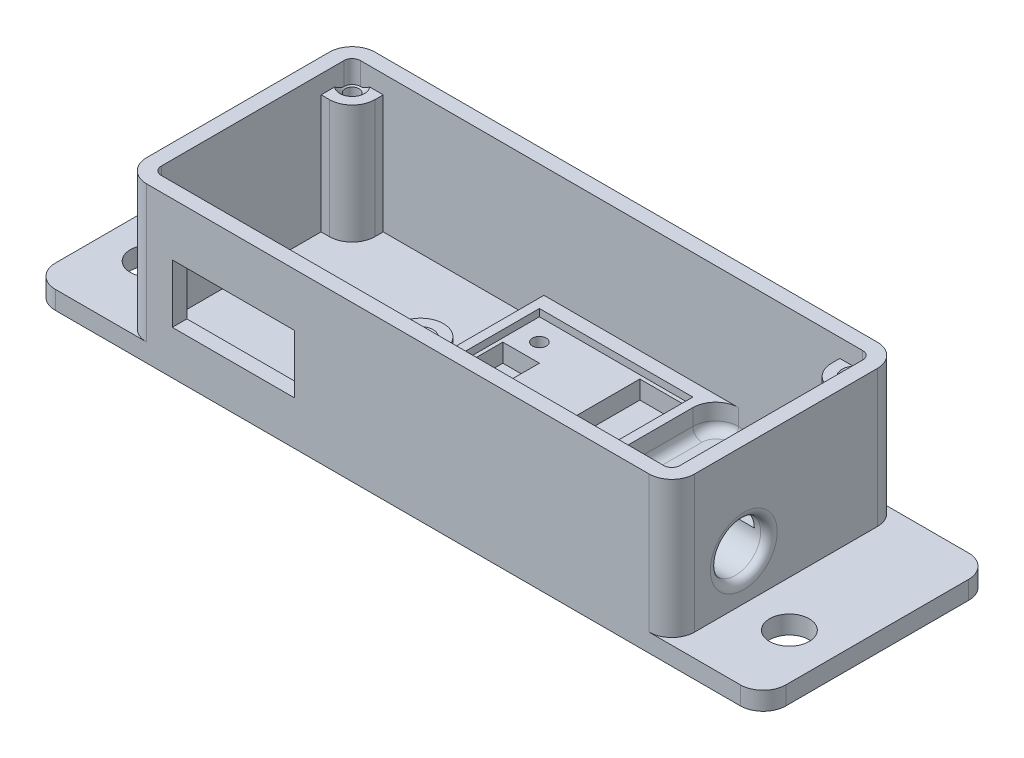
SolidWorks part; units mm, degrees
ref_plane "Plane XZ" through (0, 0, 0) normal (0, 0, 1) x (1, 0, 0)
ref_plane "Plane XY" through (0, 0, 0) normal (0, 1, 0) x (1, 0, 0)
ref_plane "Plane YZ" through (0, 0, 0) normal (1, 0, 0) x (0, 0, -1)
sketch "Sketch1" plane through (0, 0, 0) normal (0, 1, 0) x (1, 0, 0)
  line L0 (0, 15.875) -> (0, -15.875) construction
  line L1 (-50.8, 15.875) -> (50.8, 15.875)
  line L2 (-50.8, 15.875) -> (-50.8, -15.875)
  line L3 (-50.8, -15.875) -> (50.8, -15.875)
  line L4 (50.8, 15.875) -> (50.8, -15.875)
  dimension "D1" = 31.75
  dimension "D2" = 101.6
extrude "Boss-Extrude1" add sketch "Sketch1" along normal blind 2.54
sketch "Sketch2" plane through (0, 2.54, 0) normal (0, 1, 0) x (1, 0, 0)
  line L0 (-7.62, 3.175) -> (12.7, 3.175) construction
  line L1 (-7.62, 11.43) -> (12.7, 11.43)
  line L2 (-7.62, 11.43) -> (-7.62, -5.08)
  line L3 (-7.62, -5.08) -> (12.7, -5.08)
  line L4 (12.7, 11.43) -> (12.7, -5.08)
  circle A0 centre (-5.08, 8.89) radius 0.9652
  circle A1 centre (-5.08, -2.54) radius 0.9652
  dimension "D5" = 1.9304
  dimension "D1" = 20.32
  dimension "D2" = 16.51
  dimension "D3" = 2.54
  dimension "D4" = 2.54
  dimension "D6" = 7.62
  dimension "D7" = 3.175
sketch "Sketch3" plane through (0, 2.54, 0) normal (0, 1, 0) x (1, 0, 0)
  line L0 (50.8, 15.875) -> (-50.8, 15.875) construction
  line L1 (-38.1, 15.875) -> (38.1, 15.875)
  line L2 (-38.1, 15.875) -> (-38.1, -15.875)
  line L3 (-38.1, -15.875) -> (38.1, -15.875)
  line L4 (38.1, 15.875) -> (38.1, -15.875)
  line L5 (-50.8, -15.875) -> (50.8, -15.875) construction
  line L6 (0, 13.843) -> (0, -13.843) construction
  line L7 (-36.068, 13.843) -> (36.068, 13.843)
  line L8 (-36.068, 13.843) -> (-36.068, -13.843)
  line L9 (-36.068, -13.843) -> (36.068, -13.843)
  line L10 (36.068, 13.843) -> (36.068, -13.843)
  line L11 (-38.1, 0) -> (38.1, 0) construction
  dimension "D1" = 2.032
  dimension "D2" = 2.032
  dimension "D3" = 76.2
  dimension "D4" = 27.686
extrude "Boss-Extrude2" add sketch "Sketch3" along normal blind 19.05
sketch "Sketch4" plane through (-24.892, 0, 15.875) normal (0, 0, -1) x (-1, 0, 0)
  line L0 (-2.032, 17.2403) -> (-2.032, 3.0797) construction
  line L1 (-13.8748, 17.2402) -> (9.8107, 17.2402) construction
  line L2 (-13.8748, 17.2402) -> (-13.8747, 3.0797) construction
  line L3 (-13.8747, 3.0797) -> (9.8108, 3.0798) construction
  line L4 (9.8107, 17.2402) -> (9.8108, 3.0798) construction
  line L5 (-10.541, 14.224) -> (6.477, 14.224)
  line L6 (-10.541, 14.224) -> (-10.541, 6.096)
  line L7 (-10.541, 6.096) -> (6.477, 6.096)
  line L8 (6.477, 14.224) -> (6.477, 6.096)
  line L9 (-10.541, 10.16) -> (6.477, 10.16) construction
  line L10 (-2.032, 3.0797) -> (-2.032, 0.5764) construction
  line L12 (25.908, 2.54) -> (13.208, 2.54) construction
  line L13 (13.208, 21.59) -> (13.208, 2.54) construction
  point P12 (-2.032, 10.16)
  dimension "D1" = 8.128
  dimension "D2" = 17.018
  dimension "D3" = 23.6855
  dimension "D4" = 14.1605
  dimension "D5" = 7.62
  dimension "D6" = 15.24
extrude "Cut-Extrude1" cut sketch "Sketch4" along normal blind 19.05
sketch "Sketch7" plane through (36.068, 0, 0) normal (-1, 0, 0) x (0, 0, 1)
  line L0 (15.875, 21.59) -> (15.875, 2.54) construction
  line L1 (13.843, 2.54) -> (-13.843, 2.54) construction
  circle A0 centre (5.875, 8.89) radius 3.5052
  dimension "D1" = 7.0104
  dimension "D2" = 10
  dimension "D3" = 6.35
fillet "Fillet1" radius 3.175 4 edges at (38.1, 12.065, -15.875) (38.1, 12.065, 15.875) (-38.1, 12.065, -15.875) (-38.1, 12.065, 15.875)
fillet "Fillet2" radius 1.143 4 edges at (-36.068, 12.065, -13.843) (36.068, 12.065, 13.843) (36.068, 12.065, -13.843) (-36.068, 12.065, 13.843)
ref_plane "Plane1" through (0, 0, -3.285) normal (0, 0, 1) x (1, 0, 0)
sketch "Sketch8" plane through (0, 2.54, 0) normal (0, 1, 0) x (1, 0, 0)
  line L0 (34.925, 13.843) -> (-34.925, 13.843) construction
  line L1 (-9.398, 13.843) -> (14.478, 13.843)
  line L2 (-9.398, 13.843) -> (-9.398, -13.843)
  line L3 (-9.398, -13.843) -> (14.478, -13.843)
  line L4 (14.478, 13.843) -> (14.478, -13.843)
  line L5 (-34.925, -13.843) -> (34.925, -13.843) construction
  line L6 (-7.62, 11.43) -> (-7.62, -5.08) construction
  line L7 (12.7, 11.43) -> (12.7, -5.08) construction
  circle A0 centre (-5.08, 8.89) radius 0.9652 construction
  circle A1 centre (-5.08, 8.89) radius 0.9652
  circle A2 centre (-5.08, -2.54) radius 0.9652 construction
  circle A3 centre (-5.08, -2.54) radius 0.9652
  dimension "D1" = 1.778
  dimension "D2" = 1.778
extrude "Boss-Extrude3" add sketch "Sketch8" along normal blind 2.54
sketch "Sketch9" plane through (0, 5.08, 0) normal (0, 1, 0) x (1, 0, 0)
  line L2 (-7.62, 6.35) -> (-2.54, 6.35)
  line L3 (-7.62, 6.35) -> (-7.62, 0)
  line L4 (-7.62, 0) -> (-2.54, 0)
  line L5 (-2.54, 6.35) -> (-2.54, 0)
  line L6 (-7.62, 11.43) -> (-7.62, -5.08) construction
  line L7 (-7.62, -5.08) -> (12.7, -5.08) construction
  line L8 (12.7, 11.43) -> (6.35, 11.43)
  line L9 (12.7, 11.43) -> (12.7, -5.08)
  line L10 (12.7, -5.08) -> (6.35, -5.08)
  line L11 (6.35, 11.43) -> (6.35, -5.08)
  circle A0 centre (-5.08, -2.54) radius 2.54 construction
  circle A1 centre (-5.08, 8.89) radius 2.54 construction
  dimension "D1" = 5.08
  dimension "D2" = 5.08
  dimension "D3" = 5.08
  dimension "D4" = 6.35
extrude "Cut-Extrude2" cut sketch "Sketch9" against normal up to surface (2.54 mm away) up to face at (-26.8759, 2.54, 0)
sketch "Sketch10" plane through (0, 5.08, 0) normal (0, 1, 0) x (1, 0, 0)
  line L4 (-9.398, 13.843) -> (-9.398, -13.843)
  line L5 (-9.398, -13.843) -> (14.478, -13.843)
  line L6 (14.478, -13.843) -> (14.478, 13.843)
  line L7 (14.478, 13.843) -> (-9.398, 13.843)
  line L8 (-9.398, 13.843) -> (-9.398, -13.843)
  line L9 (-9.398, -13.843) -> (14.478, -13.843)
  line L10 (14.478, -13.843) -> (14.478, 13.843)
  line L11 (14.478, 13.843) -> (-9.398, 13.843)
  line L16 (13.208, -5.588) -> (13.208, 11.938)
  line L17 (-8.128, -5.588) -> (13.208, -5.588)
  line L18 (-8.128, 11.938) -> (-8.128, -5.588)
  line L19 (13.208, 11.938) -> (-8.128, 11.938)
  line L20 (13.208, -5.588) -> (13.208, 11.938)
  line L21 (-8.128, -5.588) -> (13.208, -5.588)
  line L22 (-8.128, 11.938) -> (-8.128, -5.588)
  line L23 (13.208, 11.938) -> (-8.128, 11.938)
  dimension "D1" = 0
  dimension "D2" = 0.508
extrude "Boss-Extrude4" add sketch "Sketch10" along normal blind 1
extrude "Cut-Extrude3" cut sketch "Sketch7" against normal through all
sketch "Sketch11" plane through (36.068, 0, 0) normal (-1, 0, 0) x (0, 0, 1)
  line L0 (9.3802, 8.89) -> (13.843, 8.89)
  line L1 (13.843, 8.89) -> (13.843, 2.54)
  line L2 (13.843, 2.54) -> (-2.7102, 2.54)
  line L3 (-2.7102, 2.54) -> (-2.7102, 8.89)
  line L4 (-2.7102, 8.89) -> (2.3698, 8.89)
  line L5 (13.843, 21.59) -> (13.843, 2.54) construction
  line L6 (12.7, 2.54) -> (-12.7, 2.54) construction
  circle A0 centre (5.875, 8.89) radius 3.5052 construction
  circle A1 centre (5.875, 8.89) radius 3.5052 construction
  arc A2 (2.3698, 8.89) -> (9.3802, 8.89) centre (5.875, 8.89) ccw
  dimension "D1" = 5.08
extrude "Boss-Extrude5" add sketch "Sketch11" along normal blind 10.16
sketch "Sketch13" plane through (0, 8.89, 0) normal (0, 1, 0) x (1, 0, 0)
  line L0 (25.908, -9.3802) -> (36.068, -9.3802) construction
  line L1 (33.528, -11.1582) -> (29.083, -11.1582)
  line L2 (33.528, -11.1582) -> (33.528, -13.0632)
  line L3 (33.528, -13.0632) -> (29.083, -13.0632)
  line L4 (29.083, -11.1582) -> (29.083, -13.0632)
  line L5 (36.068, -12.7) -> (36.068, -9.3802) construction
  dimension "D1" = 1.778
  dimension "D2" = 4.445
  dimension "D3" = 1.905
  dimension "D4" = 2.54
ref_axis "Axis1" through (38.1, 8.89, 5.875) along (-1, 0, 0)
revolve "Cut-Revolve1" cut sketch "Sketch13" angle 360 about axis through (38.1, 8.89, 5.875) along (-1, 0, 0)
fillet "Fillet3" radius 1.143 1 edges at (38.1, 8.89, 9.3802)
sketch "Sketch14" plane through (0, 6.096, 0) normal (0, 1, 0) x (1, 0, 0)
  line L0 (-7.85, 3.285) -> (7.85, 3.285) construction
  line L1 (-31.369, -15.875) -> (-14.351, -15.875)
  line L2 (-31.369, -15.875) -> (-31.369, 3.285)
  line L3 (-31.369, 3.285) -> (-14.351, 3.285)
  line L4 (-14.351, -15.875) -> (-14.351, 3.285)
fillet "Fillet4" radius 1.143 1 edges at (25.908, 5.3848, 5.875)
sketch "Sketch15" plane through (0, 2.54, 0) normal (0, 1, 0) x (1, 0, 0)
  line L0 (-38.1, 0) -> (-50.8, 0) construction
  line L1 (-38.1, 12.7) -> (-38.1, -12.7) construction
  line L2 (-50.8, 15.875) -> (-50.8, -15.875) construction
  line L3 (-44.45, 0) -> (-44.45, -5.875) construction
  line L4 (-50.8, -15.875) -> (-34.925, -15.875) construction
  line L5 (38.1, 0) -> (50.8, 0) construction
  line L6 (38.1, -12.7) -> (38.1, 12.7) construction
  line L7 (50.8, -15.875) -> (50.8, 15.875) construction
  line L8 (44.45, 0) -> (44.45, -5.875) construction
  line L9 (34.925, -15.875) -> (50.8, -15.875) construction
  circle A0 centre (-44.45, -5.875) radius 2.75
  circle A1 centre (44.45, -5.875) radius 2.75
  dimension "D2" = 5.5
  dimension "D1" = 10
  dimension "D3" = 10
extrude "Cut-Extrude4" cut sketch "Sketch15" against normal through all
fillet "Fillet5" radius 3.175 4 edges at (-50.8, 1.27, -15.875) (-50.8, 1.27, 15.875) (50.8, 1.27, -15.875) (50.8, 1.27, 15.875)
fillet "Fillet6" radius 3.175 1 edges at (25.908, 5.715, -2.7102)
fillet "Fillet7" radius 3.175 2 edges at (14.478, 4.31, 13.843) (14.478, 4.31, -13.843)
fillet "Fillet8" radius 1.27 7 edges at (36.068, 2.54, -7.7051) (35.7332, 2.54, -13.5082) (21.7805, 2.54, 13.843) (15.4079, 2.54, 12.9131) (14.478, 2.54, 0) (15.4079, 2.54, -12.9131) (26.289, 2.54, -13.843)
ref_plane "Plane2" through (0, 19.05, 0) normal (0, 1, 0) x (1, 0, 0)
sketch "Sketch17" plane through (0, 19.05, 0) normal (0, 1, 0) x (1, 0, 0)
  line L0 (-38.1, 12.7) -> (-38.1, -12.7) construction
  line L1 (34.925, 15.875) -> (-34.925, 15.875) construction
  line L3 (0, 0) -> (0, -12.7) construction
  line L4 (-34.925, -15.875) -> (34.925, -15.875) construction
  line L5 (-3.175, -12.7) -> (-3.175, -13.843)
  line L6 (-34.925, -13.843) -> (34.925, -13.843) construction
  line L7 (-3.175, -13.843) -> (3.175, -13.843)
  line L8 (-9.398, -13.843) -> (17.653, -13.843) construction
  line L9 (3.175, -13.843) -> (3.175, -12.7)
  line L10 (-34.925, 9.525) -> (-36.068, 9.525)
  line L11 (-36.068, 12.7) -> (-36.068, -12.7) construction
  line L12 (-36.068, 9.525) -> (-36.068, 13.843)
  line L13 (-36.068, 13.843) -> (-31.75, 13.843)
  line L14 (-31.75, 13.843) -> (-31.75, 12.7)
  line L15 (-9.398, 13.843) -> (-34.925, 13.843) construction
  line L16 (34.925, 9.525) -> (36.068, 9.525)
  line L17 (36.068, 9.525) -> (36.068, 13.843)
  line L18 (36.068, 13.843) -> (31.75, 13.843)
  line L19 (31.75, 13.843) -> (31.75, 12.7)
  circle A0 centre (-34.925, 12.7) radius 3.175 construction
  circle A1 centre (-34.925, 12.7) radius 0.9652
  circle A2 centre (0, -12.7) radius 3.175 construction
  circle A3 centre (0, -12.7) radius 0.9652
  arc A6 (-3.175, -12.7) -> (3.175, -12.7) centre (0, -12.7) cw
  arc A7 (-34.925, 9.525) -> (-31.75, 12.7) centre (-34.925, 12.7) ccw
  circle A8 centre (34.925, 12.7) radius 0.9652
  arc A9 (34.925, 9.525) -> (31.75, 12.7) centre (34.925, 12.7) cw
  dimension "D1" = 1.9304
  dimension "D2" = 6.35
extrude "Boss-Extrude6" add sketch "Sketch17" against normal up to surface (16.51 mm away) up to face at (-26.8759, 2.54, 0)
chamfer "Chamfer1" distance 0.762 angle 45 3 edges at (0, 19.05, 13.6652) (34.925, 19.05, -13.6652) (-34.925, 19.05, -11.7348)
